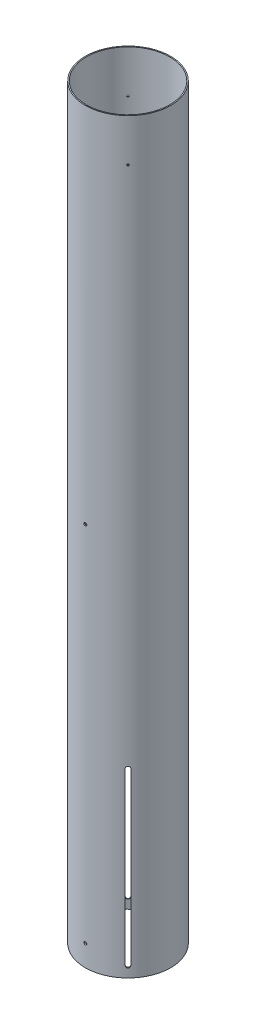
SolidWorks part; units mm, degrees
material "Wildman Fiberglass"
ref_plane "Front Plane" through (0, 0, 0) normal (0, 0, 1) x (1, 0, 0)
ref_plane "Top Plane" through (0, 0, 0) normal (0, 1, 0) x (1, 0, 0)
ref_plane "Right Plane" through (0, 0, 0) normal (1, 0, 0) x (0, 0, -1)
sketch "Sketch1" plane through (0, 0, 0) normal (0, 1, 0) x (1, 0, 0)
  circle A0 centre (0, 0) radius 49.53
  circle A1 centre (0, 0) radius 50.8
  dimension "D1" = 101.6
  dimension "D2" = 99.06
extrude "Boss-Extrude1" add sketch "Sketch1" along normal blind 889
extrude "Cut-Extrude1" cut sketch "Sketch2" against normal blind 152.4
sketch "Sketch2" plane through (1.0217, 1243.3556, -179.1581) normal (0.7071, 0, -0.7071) x (0, 1, 0)
  line L0 (-1230.6556, 128.3427) -> (-1027.4556, 128.3427)
  line L1 (-1027.4556, 123.5802) -> (-1230.6556, 123.5802)
  arc A0 (-1230.6556, 128.3427) -> (-1230.6556, 123.5802) centre (-1230.6556, 125.9615) ccw
  arc A1 (-1027.4556, 128.3427) -> (-1027.4556, 123.5802) centre (-1027.4556, 125.9615) cw
pattern_circular "CirPattern1" count 4 over 360 about axis through (0, 889, 0) along (0, -1, 0) of "Cut-Extrude1" reverse direction yes
extrude "Cut-Extrude2" cut sketch "Sketch3" against normal blind 11.684
sketch "Sketch3" plane through (271.0916, 1243.3556, 52.3875) normal (0, 0, 1) x (-1, 0, 0)
  circle A0 centre (271.0916, 1217.9556) radius 1.7653
  circle A2 centre (271.0916, 786.1556) radius 1.7653
extrude "Cut-Extrude3" cut sketch "Sketch4" against normal blind 25.4
sketch "Sketch4" plane through (120.5803, 708.4046, -48.7382) normal (0.7071, 0, 0.7071) x (-0.7071, 0, 0.7071)
  line L0 (68.9263, -129.7954) -> (170.5263, -129.7954) construction
  circle A0 centre (119.7263, -129.7954) radius 1.0922
  point P8 (0, 0)
  point P9 (0, 0)
pattern_circular "CirPattern2" count 2 over 360 about axis through (0, 889, 0) along (0, -1, 0) of "Cut-Extrude3"
equation "\"Length\"=35"
equation "\"D1@Boss-Extrude1\"=\"Length\""
